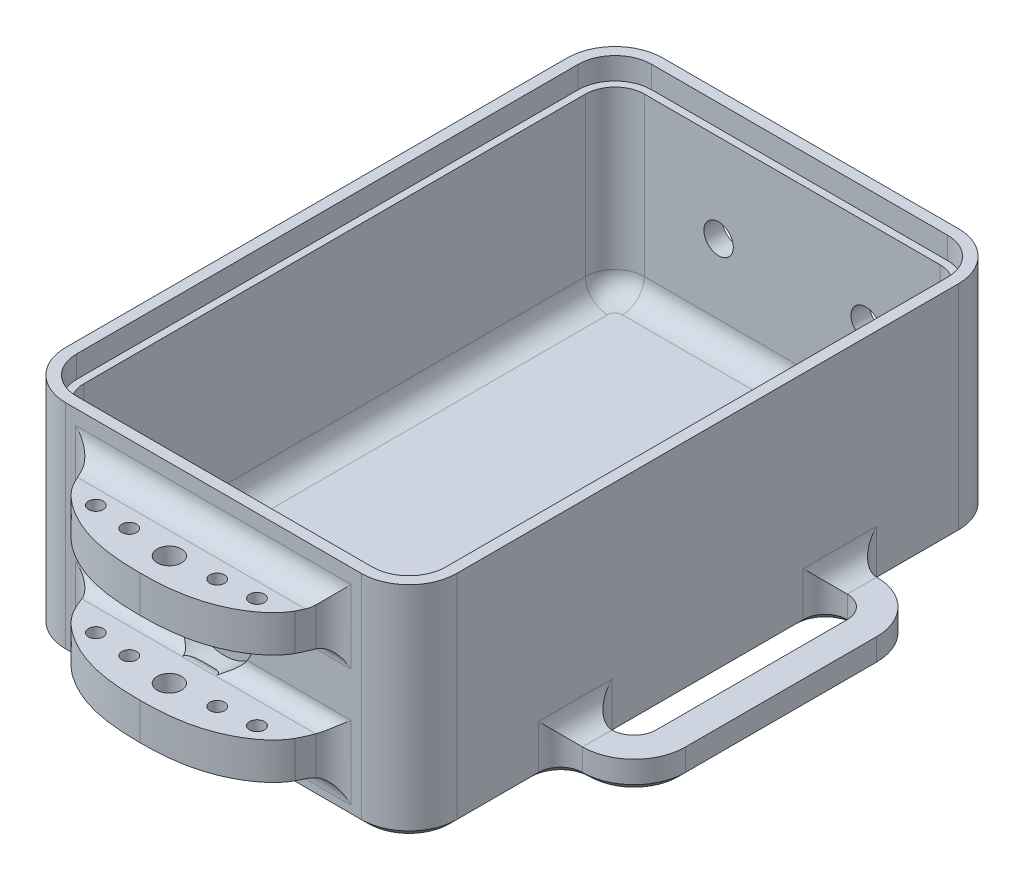
SolidWorks part; units mm, degrees
ref_plane "Front Plane" through (0, 0, 0) normal (0, 0, 1) x (1, 0, 0)
ref_plane "Top Plane" through (0, 0, 0) normal (0, 1, 0) x (1, 0, 0)
ref_plane "Right Plane" through (0, 0, 0) normal (1, 0, 0) x (0, 0, -1)
sketch "Sketch1" plane through (0, 0, 0) normal (0, 1, 0) x (1, 0, 0)
  line L0 (0, 36.2013) -> (0, -37.8247) construction
  line L1 (-30.7359, 0) -> (33.658, 0) construction
  line L3 (-20.1, -39.1) -> (20.1, -39.1)
  line L4 (-25.1, -34.1) -> (-25.1, 34.1)
  line L5 (-20.1, 39.1) -> (20.1, 39.1)
  line L6 (25.1, -34.1) -> (25.1, 34.1)
  line L7 (-25.1, -39.1) -> (25.1, 39.1) construction
  line L8 (-25.1, 39.1) -> (25.1, -39.1) construction
  line L9 (-20.1, -38.1) -> (20.1, -38.1)
  line L10 (-24.1, -34.1) -> (-24.1, 34.1)
  line L11 (-20.1, 38.1) -> (20.1, 38.1)
  line L12 (24.1, -34.1) -> (24.1, 34.1)
  line L13 (-24.1, -38.1) -> (24.1, 38.1) construction
  line L14 (-24.1, 38.1) -> (24.1, -38.1) construction
  line L15 (-20.1, -40.6) -> (20.1, -40.6)
  line L16 (-26.6, -34.1) -> (-26.6, 34.1)
  line L17 (-20.1, 40.6) -> (20.1, 40.6)
  line L18 (26.6, -34.1) -> (26.6, 34.1)
  line L19 (-26.6, -40.6) -> (26.6, 40.6) construction
  line L20 (-26.6, 40.6) -> (26.6, -40.6) construction
  arc A0 (25.1, -34.1) -> (20.1, -39.1) centre (20.1, -34.1) cw
  arc A1 (-20.1, -39.1) -> (-25.1, -34.1) centre (-20.1, -34.1) cw
  arc A2 (25.1, 34.1) -> (20.1, 39.1) centre (20.1, 34.1) ccw
  arc A3 (-20.1, 39.1) -> (-25.1, 34.1) centre (-20.1, 34.1) ccw
  arc A4 (-20.1, -38.1) -> (-24.1, -34.1) centre (-20.1, -34.1) cw
  arc A5 (24.1, -34.1) -> (20.1, -38.1) centre (20.1, -34.1) cw
  arc A6 (24.1, 34.1) -> (20.1, 38.1) centre (20.1, 34.1) ccw
  arc A7 (-20.1, 38.1) -> (-24.1, 34.1) centre (-20.1, 34.1) ccw
  arc A8 (-20.1, -40.6) -> (-26.6, -34.1) centre (-20.1, -34.1) cw
  arc A9 (26.6, -34.1) -> (20.1, -40.6) centre (20.1, -34.1) cw
  arc A10 (26.6, 34.1) -> (20.1, 40.6) centre (20.1, 34.1) ccw
  arc A11 (-20.1, 40.6) -> (-26.6, 34.1) centre (-20.1, 34.1) ccw
  point P5 (0, 0)
  point P22 (0, 0)
  point P40 (0, 0)
  dimension "D3" = 5
  dimension "D6" = 4
  dimension "D9" = 6.5
  dimension "D1" = 50.2
  dimension "D2" = 78.2
  dimension "D4" = 1
  dimension "D5" = 1
  dimension "D7" = 1.5
  dimension "D8" = 1.5
extrude "Boss-Extrude1" add sketch "Sketch1" along normal blind 30 contours L17 A11 L16 A8 L15 A9 L18 A10 A3 L5 A2 L6 A0 L3 A1 L4 region at (-24.0098, 0, 38.0098)
extrude "Boss-Extrude2" add sketch "Sketch1<3>" along normal blind 27 contours L5 A3 L4 A1 L3 A0 L6 A2 A7 L11 A6 L12 A5 L9 A4 L10 region at (-22.9784, 0, 36.9784)
sketch "Sketch1<3>" plane through (0, 0, 0) normal (0, 1, 0) x (1, 0, 0) same geometry as "Sketch1"
extrude "Boss-Extrude3" add sketch "Sketch1<4>" along normal blind 2.5 contours L11 A7 L10 A4 L9 A5 L12 A6 region at (0, 0, 0)
sketch "Sketch1<4>" plane through (0, 0, 0) normal (0, 1, 0) x (1, 0, 0) same geometry as "Sketch1"
fillet "Fillet1" radius 3 8 edges at (22.9284, 2.5, -36.9284) (24.1, 2.5, 0) (22.9284, 2.5, 36.9284) (0, 2.5, 38.1) (-22.9284, 2.5, 36.9284) (-24.1, 2.5, 0) (-22.9284, 2.5, -36.9284) (0, 2.5, -38.1)
sketch "Sketch3" plane through (0, 0, -40.6) normal (0, 0, -1) x (-1, 0, 0)
  line L0 (-31.6909, 15) -> (38.2468, 15) construction
  line L1 (0, 0) -> (0, 30) construction
  line L2 (20.1, 0) -> (-20.1, 0) construction
  line L3 (20.1, 30) -> (-20.1, 30) construction
  circle A0 centre (-10, 15) radius 2
  circle A1 centre (10, 15) radius 2
  point P8 (0, 15)
  dimension "D1" = 4
  dimension "D2" = 20
extrude "Bornier" cut sketch "Sketch3" against normal up to next
sketch "Sketch4" plane through (0, 0, 0) normal (0, -1, 0) x (1, 0, 0)
  line L0 (26.6, 34.1) -> (26.6, -34.1) construction
  line L1 (32.6, 16) -> (26.6, 16)
  line L2 (32.6, 16) -> (32.6, -16)
  line L3 (32.6, -16) -> (26.6, -16)
  line L4 (26.6, 16) -> (26.6, -16)
  line L5 (32.6, 16) -> (26.6, -16) construction
  line L6 (32.6, -16) -> (26.6, 16) construction
  line L7 (0, 0) -> (58.1127, 0) construction
  line L8 (26.6, -20) -> (36.6, -20)
  line L13 (-26.6, 20) -> (-26.6, 16)
  line L14 (-32.6, 16) -> (-26.6, 16)
  line L15 (36.6, -20) -> (36.6, 20)
  line L16 (36.6, 20) -> (26.6, 20)
  line L17 (26.6, 20) -> (26.6, 16)
  line L18 (26.6, -20) -> (26.6, -16)
  line L19 (0, 0) -> (0, -47.7172) construction
  line L20 (-36.6, -20) -> (-36.6, 20)
  line L21 (-36.6, 20) -> (-26.6, 20)
  line L22 (-26.6, -20) -> (-36.6, -20)
  line L23 (-26.6, -20) -> (-26.6, -16)
  line L24 (-32.6, -16) -> (-26.6, -16)
  line L25 (-32.6, 16) -> (-32.6, -16)
  point P0 (29.6, 0)
  line M13 (26.6, -34.1) -> (26.6, 34.1)
  line M17 (-26.6, 34.1) -> (-26.6, -34.1)
  dimension "D1" = 6
  dimension "D2" = 4
  dimension "D3" = 4
  dimension "D4" = 40
extrude "Boss-Extrude4" add sketch "Sketch4" against normal blind 4 contours L15 L16 L1 L2 L3 L8 M13 | L25 L14 L21 L20 L22 L24 M17 region at (33.4462, 0, 0) region at (-33.4462, 0, 0)
fillet "Fillet2" radius 3 16 edges at (32.6, 2, 16) (32.6, 2, -16) (26.6, 2, -20) (26.6, 2, -16) (26.6, 4, -18) (26.6, 4, 18) (26.6, 2, 20) (26.6, 2, 16) (-32.6, 2, -16) (-26.6, 2, -20) (-26.6, 4, -18) (-26.6, 2, -16) (-26.6, 4, 18) (-26.6, 2, 20) (-26.6, 2, 16) (-32.6, 2, 16)
fillet "Fillet3" radius 7 4 edges at (-36.6, 2, -20) (-36.6, 2, 20) (36.6, 2, -20) (36.6, 2, 20)
ref_plane "Plane1" through (0, 15, 0) normal (0, -1, 0) x (-1, 0, 0)
sketch "Sketch5" plane through (0, 15, 0) normal (0, -1, 0) x (-1, 0, 0)
  line L0 (0, 0) -> (0, -62.5379) construction
  line L1 (16.5227, -40.6) -> (-16.5227, -40.6)
  line L2 (20.1, -40.6) -> (-20.1, -40.6) construction
  line L3 (20.1, -38.1) -> (-20.1, -38.1) construction
  line L5 (0, -46.6) -> (-26.3183, -44.2974) construction
  arc A0 (-16.5227, -40.6) -> (-15.0258, -44.5515) centre (0, -36.6) ccw
  circle A1 centre (0, -46.6) radius 1.65
  circle A2 centre (-5.9772, -46.0771) radius 1
  circle A3 centre (-10.9581, -45.6413) radius 1
  circle A4 centre (10.9581, -45.6413) radius 1
  circle A5 centre (5.9772, -46.0771) radius 1
  arc A6 (15.0258, -44.5515) -> (16.5227, -40.6) centre (0, -36.6) ccw
  spline S0 degree 3 poles (-15.0258, -44.5515) (-14.2287, -46.0577) (-9.3456, -49.9684) (-3.8447, -50.6007) (0, -50.6007) knots 0 0 0 0 0.327379 1 1 1 1
  spline S1 degree 3 poles (15.0258, -44.5515) (14.2287, -46.0577) (9.3456, -49.9684) (3.8447, -50.6007) (0, -50.6007) knots 0 0 0 0 0.327379 1 1 1 1
  dimension "D2" = 17
  dimension "D3" = 3.3
  dimension "D6" = 2
  dimension "D7" = 2
  dimension "D1" = 1.5
  dimension "D4" = 10
  dimension "D5" = 85
  dimension "D8" = 6
  dimension "D9" = 5
extrude "Boss-Extrude6" add sketch "Sketch5" along normal blind 10 and the other way blind 10
sketch "Sketch6" plane through (0, 0, 0) normal (1, 0, 0) x (0, 0, -1)
  line L0 (-40.6, 30) -> (-40.6, 0) construction
  line L1 (-50.6007, 10) -> (-40.6, 10)
  line L2 (-50.6007, 10) -> (-50.6007, 20)
  line L3 (-50.6007, 20) -> (-40.6, 20)
  line L4 (-40.6, 10) -> (-40.6, 20)
  line L5 (-50.6007, 10) -> (-40.6, 20) construction
  line L6 (-50.6007, 20) -> (-40.6, 10) construction
  line L8 (-4.0719, 15) -> (-59.9731, 15) construction
  line L9 (-40.26, 15) -> (40.26, 15) construction
  line L11 (-50.6007, 25) -> (-50.6007, 5) construction
  point P0 (-45.6003, 15)
  dimension "D1" = 10
extrude "Cut-Extrude2" cut sketch "Sketch6" against normal through all both and the other way through all
fillet "Fillet4" radius 3 6 edges at (16.5227, 7.5, 40.6) (0, 5, 40.6) (16.5227, 22.5, 40.6) (0, 25, 40.6) (-16.5227, 7.5, 40.6) (-16.5227, 22.5, 40.6)
sketch "Sketch7" plane through (0, 0, 40.6) normal (0, 0, 1) x (1, 0, 0)
  line L0 (0, 0) -> (0, 30) construction
  line L1 (-20.1, 0) -> (20.1, 0) construction
  line L2 (18.6652, 15) -> (-18.6652, 15) construction
  line L3 (-40.26, 15) -> (40.26, 15) construction
  line L5 (-6.0208, 18) -> (-13, 18)
  line L6 (-13, 18) -> (-13, 12)
  line L7 (-13, 12) -> (-6.0208, 12)
  line L8 (-9, 18) -> (-9, 12)
  arc A0 (-3.8958, 11.1176) -> (-3.8958, 18.8824) centre (0, 15) ccw
  arc A1 (-6.0208, 12) -> (-3.8958, 11.1176) centre (-6.0208, 9) cw
  arc A2 (-6.0208, 18) -> (-3.8958, 18.8824) centre (-6.0208, 21) ccw
  point P8 (0, 15)
  point P9 (0, 15)
  line M10 (-18.735, 10) -> (18.735, 10)
  line M19 (18.735, 20) -> (-18.735, 20)
  dimension "D1" = 11
  dimension "D5" = 3
  dimension "D2" = 6
  dimension "D3" = 13
  dimension "D4" = 4
extrude "Cut-Extrude3" cut sketch "Sketch7" against normal blind 1.5 contours A2 L5 L8 L7 A1 A0 M10 M19 | A0 A2 L5 L6 L7 A1 region at (-1.4206, 15, 40.6)
extrude "Cut-Extrude4" cut sketch "Sketch7<3>" against normal up to next contours L8 L5 L6 L7 region at (-11, 15, 40.6)
sketch "Sketch7<3>" plane through (0, 0, 40.6) normal (0, 0, 1) x (1, 0, 0) same geometry as "Sketch7"
fillet "Fillet5" radius 2 2 edges at (0, 10, 40.6) (0, 20, 40.6)
fillet "Fillet6" radius 2 4 edges at (-10.5131, 20, 40.6) (10.5131, 20, 40.6) (-10.5131, 10, 40.6) (10.5131, 10, 40.6)
chamfer "Chamfer1" distance 1 angle 45 32 edges at (-31.7213, 0, -15.1213) (-27.4787, 0, -15.1213) (-26.6, 0, 0) (-27.4787, 0, 15.1213) (-31.7213, 0, 15.1213) (-32.6, 0, 0) (32.6, 0, 0) (31.7213, 0, 15.1213) (27.4787, 0, 15.1213) (26.6, 0, 0) (27.4787, 0, -15.1213) (31.7213, 0, -15.1213) (-34.5497, 0, 17.9497) (-27.4787, 0, 20.8787) (-26.6, 0, 28.55) (-24.6962, 0, 38.6962) (0, 0, 40.6) (24.6962, 0, 38.6962) (26.6, 0, 28.55) (27.4787, 0, 20.8787) (34.5497, 0, 17.9497) (36.6, 0, 0) (34.5497, 0, -17.9497) (27.4787, 0, -20.8787) (26.6, 0, -28.55) (24.6962, 0, -38.6962) (0, 0, -40.6) (-24.6962, 0, -38.6962) (-26.6, 0, -28.55) (-27.4787, 0, -20.8787) (-34.5497, 0, -17.9497) (-36.6, 0, 0)
